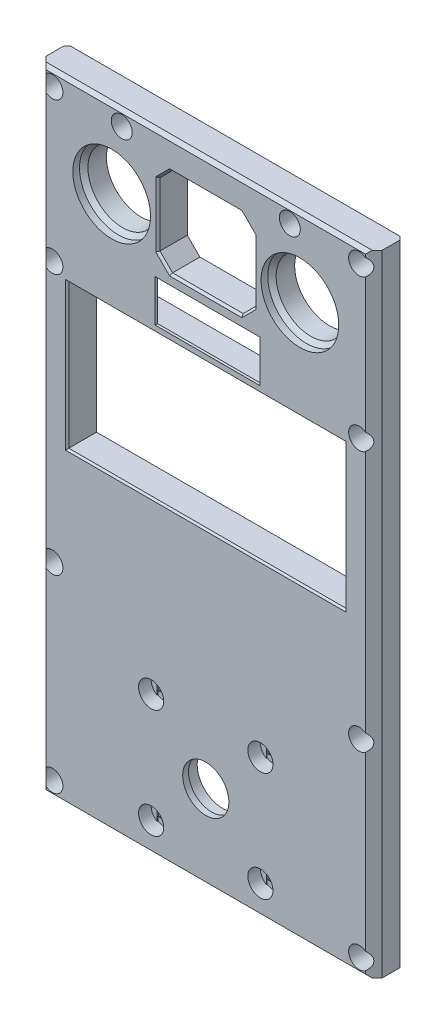
SolidWorks part; units mm, degrees
ref_plane "Front Plane" through (0, 0, 0) normal (0, 0, 1) x (1, 0, 0)
ref_plane "Top Plane" through (0, 0, 0) normal (0, 1, 0) x (1, 0, 0)
ref_plane "Right Plane" through (0, 0, 0) normal (1, 0, 0) x (0, 0, -1)
sketch "Sketch1" plane through (0, 0, 0) normal (0, 0, 1) x (1, 0, 0)
  line L1 (-40, -75) -> (40, -75)
  line L2 (-40, -75) -> (-40, 75)
  line L3 (-40, 75) -> (40, 75)
  line L4 (40, -75) -> (40, 75)
  line L5 (-40, -75) -> (40, 75) construction
  line L6 (-40, 75) -> (40, -75) construction
  line L7 (-33, -68) -> (33, -68)
  line L8 (-33, -68) -> (-33, 68)
  line L9 (-33, 68) -> (33, 68)
  line L10 (33, -68) -> (33, 68)
  line L11 (-33, -68) -> (33, 68) construction
  line L12 (-33, 68) -> (33, -68) construction
  point P0 (0, 0)
  point P6 (0, 0)
  dimension "D1" = 150
  dimension "D2" = 80
  dimension "D3" = 7
  dimension "D4" = 7
extrude "Boss-Extrude1" add sketch "Sketch1" along normal blind 7
sketch "Sketch2" plane through (0, 0, 7) normal (0, 0, 1) x (1, 0, 0)
  line L0 (33, -68) -> (33, 68) construction
  line L1 (-33, -68) -> (33, -68)
  line L2 (-33, -68) -> (-33, -32)
  line L3 (-33, -32) -> (33, -32)
  line L4 (33, -68) -> (33, -32)
  dimension "D1" = 36
extrude "Boss-Extrude2" add sketch "Sketch2" against normal up to surface (7 mm away) up to face at (0, 0, 0)
sketch "Sketch3" plane through (0, 0, 0) normal (0, 0, -1) x (-1, 0, 0)
  line L0 (0, -75) -> (0, -55) construction
  line L1 (40, -75) -> (-40, -75) construction
  circle A0 centre (0, -55) radius 5.5
  dimension "D1" = 11
  dimension "D2" = 20
extrude "Cut-Extrude1" cut sketch "Sketch3" against normal through all
sketch "Sketch4" plane through (0, 0, 0) normal (0, 0, -1) x (-1, 0, 0)
  circle A0 centre (0, -55) radius 6.05
  dimension "D1" = 12.1
extrude "Cut-Extrude2" cut sketch "Sketch4" against normal offset from surface (5.6 mm away) 1.4 up to face at (-5.5, -55, 7)
sketch "Sketch5" plane through (0, 0, 0) normal (0, 0, -1) x (-1, 0, 0)
  circle A0 centre (0, -55) radius 11.1
  dimension "D1" = 22.2
extrude "Cut-Extrude3" cut sketch "Sketch5" against normal offset from surface (3 mm away) 2.6 up to face at (-6.05, -55, 5.6)
sketch "Sketch6" plane through (0, 0, 0) normal (0, 0, -1) x (-1, 0, 0)
  line L1 (-13, -68) -> (13, -68) construction
  line L2 (-13, -68) -> (-13, -42) construction
  line L3 (-13, -42) -> (13, -42) construction
  line L4 (13, -68) -> (13, -42) construction
  line L5 (-13, -68) -> (13, -42) construction
  line L6 (-13, -42) -> (13, -68) construction
  circle A0 centre (-13, -42) radius 1.6
  circle A1 centre (13, -42) radius 1.6
  circle A2 centre (13, -68) radius 1.6
  circle A3 centre (-13, -68) radius 1.6
  point P0 (0, -55)
  dimension "D2" = 3.2
  dimension "D1" = 26
extrude "Cut-Extrude4" cut sketch "Sketch6" against normal through all
sketch "Sketch7" plane through (0, 0, 0) normal (0, 0, -1) x (-1, 0, 0)
  line L1 (-25, -74) -> (25, -74)
  line L2 (-25, -74) -> (-25, -36)
  line L3 (-25, -36) -> (25, -36)
  line L4 (25, -74) -> (25, -36)
  line L5 (-25, -74) -> (25, -36) construction
  line L6 (-25, -36) -> (25, -74) construction
  point P0 (0, -55)
  dimension "D1" = 50
  dimension "D2" = 38
extrude "Cut-Extrude5" cut sketch "Sketch7" against normal blind 1
sketch "Sketch8" plane through (0, 0, 7) normal (0, 0, 1) x (1, 0, 0)
  circle A0 centre (-13, -42) radius 3
  circle A1 centre (13, -42) radius 3
  circle A2 centre (13, -68) radius 3
  circle A3 centre (-13, -68) radius 3
  dimension "D1" = 6
extrude "Cut-Extrude6" cut sketch "Sketch8" against normal blind 3
sketch "Sketch9" plane through (0, 0, 7) normal (0, 0, 1) x (1, 0, 0)
  line L0 (-40, 75) -> (-40, -75) construction
  line L1 (-36.5, -71.5) -> (36.5, -71.5) construction
  line L2 (-36.5, -71.5) -> (-36.5, 71.5) construction
  line L3 (-36.5, 71.5) -> (36.5, 71.5) construction
  line L4 (36.5, -71.5) -> (36.5, 71.5) construction
  line L5 (-36.5, -71.5) -> (36.5, 71.5) construction
  line L6 (-36.5, 71.5) -> (36.5, -71.5) construction
  line L7 (40, 75) -> (-40, 75) construction
  circle A0 centre (-36.5, 71.5) radius 1.35
  circle A1 centre (36.5, 71.5) radius 1.35
  circle A2 centre (36.5, -71.5) radius 1.35
  circle A3 centre (-36.5, -71.5) radius 1.35
  circle A6 centre (-36.5, 35.5) radius 1.35
  circle A7 centre (-36.5, -26.5) radius 1.35
  circle A8 centre (36.5, -26.5) radius 1.35
  circle A9 centre (36.5, 35.5) radius 1.35
  point P0 (0, 0)
  dimension "D3" = 2.7
  dimension "D4" = 45
  dimension "D5" = 36
  dimension "D1" = 3.5
  dimension "D2" = 3.5
extrude "Cut-Extrude7" cut sketch "Sketch9" against normal through all
sketch "Sketch10" plane through (0, 0, 7) normal (0, 0, 1) x (1, 0, 0)
  circle A0 centre (-36.5, 71.5) radius 2.5
  circle A1 centre (36.5, 71.5) radius 2.5
  circle A2 centre (-36.5, 35.5) radius 2.5
  circle A3 centre (-36.5, -26.5) radius 2.5
  circle A4 centre (-36.5, -71.5) radius 2.5
  circle A5 centre (36.5, -71.5) radius 2.5
  circle A6 centre (36.5, 35.5) radius 2.5
  circle A7 centre (36.5, -26.5) radius 2.5
  dimension "D1" = 5
extrude "Cut-Extrude8" cut sketch "Sketch10" against normal blind 5
chamfer "Chamfer1" distance 2 angle 45 2 edges at (-40, 0, 7) (40, 0, 7)
sketch "Sketch11" plane through (0, 0, 7) normal (0, 0, 1) x (1, 0, 0)
  line L0 (33, -32) -> (33, 68) construction
  line L1 (-33, -32) -> (33, -32)
  line L2 (-33, -32) -> (-33, -1.5)
  line L3 (-33, -1.5) -> (33, -1.5)
  line L4 (33, -32) -> (33, -1.5)
  line L5 (-38, -75) -> (38, -75) construction
  dimension "D1" = 73.5
extrude "Boss-Extrude3" add sketch "Sketch11" against normal up to surface (7 mm away) up to face at (37.85, 71.5, 0)
sketch "Sketch12" plane through (0, 0, 2) normal (0, 0, 1) x (1, 0, 0)
  line L2 (-37.85, -73.6042) -> (-37.85, -69.3958)
  line L4 (-35.15, -73.6042) -> (-35.15, -69.3958)
  line L5 (-37.85, -73.6042) -> (-35.15, -69.3958) construction
  line L6 (-37.85, -69.3958) -> (-35.15, -73.6042) construction
  line L8 (-37.85, -28.6042) -> (-37.85, -24.3958)
  line L10 (-35.15, -28.6042) -> (-35.15, -24.3958)
  line L11 (-37.85, -28.6042) -> (-35.15, -24.3958) construction
  line L12 (-37.85, -24.3958) -> (-35.15, -28.6042) construction
  line L14 (-37.85, 33.3958) -> (-37.85, 37.6042)
  line L16 (-35.15, 33.3958) -> (-35.15, 37.6042)
  line L17 (-37.85, 33.3958) -> (-35.15, 37.6042) construction
  line L18 (-37.85, 37.6042) -> (-35.15, 33.3958) construction
  line L20 (-37.85, 69.3958) -> (-37.85, 73.6042)
  line L22 (-35.15, 69.3958) -> (-35.15, 73.6042)
  line L23 (-37.85, 69.3958) -> (-35.15, 73.6042) construction
  line L24 (-37.85, 73.6042) -> (-35.15, 69.3958) construction
  arc A0 (-38, -73.5) -> (-38, -69.5) centre (-36.5, -71.5) ccw construction
  circle A1 centre (-36.5, -26.5) radius 2.5 construction
  circle A2 centre (-36.5, 35.5) radius 2.5 construction
  arc A3 (-38, 69.5) -> (-38, 73.5) centre (-36.5, 71.5) ccw construction
  circle A4 centre (-36.5, 71.5) radius 1.35 construction
  circle A5 centre (-36.5, 71.5) radius 2.5 construction
  arc A6 (-35.15, 73.6042) -> (-37.85, 73.6042) centre (-36.5, 71.5) ccw
  arc A7 (-37.85, 69.3958) -> (-35.15, 69.3958) centre (-36.5, 71.5) ccw
  circle A8 centre (-36.5, 35.5) radius 1.35 construction
  arc A9 (-37.85, 33.3958) -> (-35.15, 33.3958) centre (-36.5, 35.5) ccw
  arc A10 (-35.15, 37.6042) -> (-37.85, 37.6042) centre (-36.5, 35.5) ccw
  circle A11 centre (-36.5, -26.5) radius 1.35 construction
  arc A12 (-37.85, -28.6042) -> (-35.15, -28.6042) centre (-36.5, -26.5) ccw
  arc A13 (-35.15, -24.3958) -> (-37.85, -24.3958) centre (-36.5, -26.5) ccw
  circle A14 centre (-36.5, -71.5) radius 1.35 construction
  arc A16 (-37.85, -73.6042) -> (-35.15, -73.6042) centre (-36.5, -71.5) ccw
  arc A18 (-35.15, -69.3958) -> (-37.85, -69.3958) centre (-36.5, -71.5) ccw
  point P0 (-36.5, -71.5)
  point P9 (-36.5, -26.5)
  point P17 (-36.5, 35.5)
  point P25 (-36.5, 71.5)
extrude "Cut-Extrude9" cut sketch "Sketch12" against normal blind 0.2
sketch "Sketch13" plane through (0, 0, 1.8) normal (0, 0, 1) x (1, 0, 0)
  line L0 (-35.15, -71.5) -> (-35.15, -69.3958) construction
  line L1 (-37.85, -72.85) -> (-35.15, -72.85)
  line L2 (-37.85, -72.85) -> (-37.85, -70.15)
  line L3 (-37.85, -70.15) -> (-35.15, -70.15)
  line L4 (-35.15, -72.85) -> (-35.15, -70.15)
  line L5 (-37.85, -72.85) -> (-35.15, -70.15) construction
  line L6 (-37.85, -70.15) -> (-35.15, -72.85) construction
  line L7 (-35.15, -26.5) -> (-35.15, -24.3958) construction
  line L8 (-37.85, -27.85) -> (-35.15, -27.85)
  line L9 (-37.85, -27.85) -> (-37.85, -25.15)
  line L10 (-37.85, -25.15) -> (-35.15, -25.15)
  line L11 (-35.15, -27.85) -> (-35.15, -25.15)
  line L12 (-37.85, -27.85) -> (-35.15, -25.15) construction
  line L13 (-37.85, -25.15) -> (-35.15, -27.85) construction
  line L14 (-35.15, 33.3958) -> (-35.15, 37.6042) construction
  line L15 (-37.85, 34.15) -> (-35.15, 34.15)
  line L16 (-37.85, 34.15) -> (-37.85, 36.85)
  line L17 (-37.85, 36.85) -> (-35.15, 36.85)
  line L18 (-35.15, 34.15) -> (-35.15, 36.85)
  line L19 (-37.85, 34.15) -> (-35.15, 36.85) construction
  line L20 (-37.85, 36.85) -> (-35.15, 34.15) construction
  line L21 (-35.15, 69.3958) -> (-35.15, 73.6042) construction
  line L22 (-37.85, 70.15) -> (-35.15, 70.15)
  line L23 (-37.85, 70.15) -> (-37.85, 72.85)
  line L24 (-37.85, 72.85) -> (-35.15, 72.85)
  line L25 (-35.15, 70.15) -> (-35.15, 72.85)
  line L26 (-37.85, 70.15) -> (-35.15, 72.85) construction
  line L27 (-37.85, 72.85) -> (-35.15, 70.15) construction
  arc A0 (-35.15, -71.5) -> (-37.85, -71.5) centre (-36.5, -71.5) ccw construction
  arc A1 (-35.15, -26.5) -> (-37.85, -26.5) centre (-36.5, -26.5) ccw construction
  arc A2 (-35.15, 35.5) -> (-37.85, 35.5) centre (-36.5, 35.5) ccw construction
  arc A3 (-35.15, 71.5) -> (-37.85, 71.5) centre (-36.5, 71.5) ccw construction
  point P0 (-36.5, -71.5)
  point P11 (-36.5, -26.5)
  point P22 (-36.5, 35.5)
  point P33 (-36.5, 71.5)
extrude "Cut-Extrude10" cut sketch "Sketch13" against normal blind 0.2
sketch "Sketch14" plane through (0, 0, 4) normal (0, 0, 1) x (1, 0, 0)
  line L2 (-14.6, -44.5377) -> (-14.6, -39.4623)
  line L4 (-11.4, -44.5377) -> (-11.4, -39.4623)
  line L5 (-14.6, -44.5377) -> (-11.4, -39.4623) construction
  line L6 (-14.6, -39.4623) -> (-11.4, -44.5377) construction
  line L8 (-14.6, -70.5377) -> (-14.6, -65.4623)
  line L10 (-11.4, -70.5377) -> (-11.4, -65.4623)
  line L11 (-14.6, -70.5377) -> (-11.4, -65.4623) construction
  line L12 (-14.6, -65.4623) -> (-11.4, -70.5377) construction
  circle A0 centre (-13, -42) radius 3 construction
  circle A1 centre (-13, -68) radius 3 construction
  circle A2 centre (-13, -42) radius 3 construction
  arc A3 (-14.6, -44.5377) -> (-11.4, -44.5377) centre (-13, -42) ccw
  arc A4 (-14.6, -70.5377) -> (-11.4, -70.5377) centre (-13, -68) ccw
  circle A5 centre (-13, -42) radius 1.6 construction
  circle A6 centre (-13, -68) radius 1.6 construction
  arc A7 (-11.4, -39.4623) -> (-14.6, -39.4623) centre (-13, -42) ccw
  arc A8 (-11.4, -65.4623) -> (-14.6, -65.4623) centre (-13, -68) ccw
  point P0 (-13, -42)
  point P8 (-13, -68)
extrude "Cut-Extrude11" cut sketch "Sketch14" against normal blind 0.2
sketch "Sketch15" plane through (0, 0, 3.8) normal (0, 0, 1) x (1, 0, 0)
  line L0 (-11.4, -42) -> (-11.4, -39.4623) construction
  line L1 (-14.6, -43.6) -> (-11.4, -43.6)
  line L2 (-14.6, -43.6) -> (-14.6, -40.4)
  line L3 (-14.6, -40.4) -> (-11.4, -40.4)
  line L4 (-11.4, -43.6) -> (-11.4, -40.4)
  line L5 (-14.6, -43.6) -> (-11.4, -40.4) construction
  line L6 (-14.6, -40.4) -> (-11.4, -43.6) construction
  line L7 (-11.4, -68) -> (-11.4, -65.4623) construction
  line L8 (-14.6, -69.6) -> (-11.4, -69.6)
  line L9 (-14.6, -69.6) -> (-14.6, -66.4)
  line L10 (-14.6, -66.4) -> (-11.4, -66.4)
  line L11 (-11.4, -69.6) -> (-11.4, -66.4)
  line L12 (-14.6, -69.6) -> (-11.4, -66.4) construction
  line L13 (-14.6, -66.4) -> (-11.4, -69.6) construction
  arc A0 (-11.4, -68) -> (-14.6, -68) centre (-13, -68) ccw construction
  arc A1 (-14.6, -42) -> (-11.4, -42) centre (-13, -42) ccw construction
  point P0 (-13, -42)
  point P8 (-13, -68)
extrude "Cut-Extrude12" cut sketch "Sketch15" against normal blind 0.2
mirror "Mirror1" about plane through (0, 0, 0) normal (1, 0, 0) of "Cut-Extrude10", "Cut-Extrude11", "Cut-Extrude12", "Cut-Extrude9"
chamfer "Chamfer2" distance 0.4 angle 45 4 edges at (33, 33.25, 7) (0, 68, 7) (0, -1.5, 7) (-33, 33.25, 7)
chamfer "Chamfer3" distance 0.8 angle 45 4 edges at (-40, 0, 0) (40, 0, 0) (0, -75, 7) (0, 75, 7)
sketch "Sketch16" plane through (0, 0, 0) normal (1, 0, 0) x (0, 0, -1)
  line L0 (0, -4) -> (0, -15.4)
  line L1 (0, 75) -> (0, -75) construction
  line L2 (0, -15.4) -> (3.2, -12.2)
  line L3 (3.2, -12.2) -> (3.2, -7.2)
  line L4 (3.2, -7.2) -> (0, -4)
  line L5 (0, -15.4) -> (0, -19.4) construction
  line L6 (0.6, -7.7) -> (2.6, -7.7)
  line L7 (0.6, -7.7) -> (0.6, -11.7)
  line L8 (0.6, -11.7) -> (2.6, -11.7)
  line L9 (2.6, -7.7) -> (2.6, -11.7)
  line L10 (-1.046, -17.4) -> (12.8392, -17.4) construction
  line L11 (2.6, -27.1) -> (2.6, -23.1)
  line L12 (0.6, -23.1) -> (2.6, -23.1)
  line L13 (0.6, -27.1) -> (0.6, -23.1)
  line L14 (0.6, -27.1) -> (2.6, -27.1)
  line L15 (3.2, -27.6) -> (0, -30.8)
  line L16 (3.2, -22.6) -> (3.2, -27.6)
  line L17 (0, -19.4) -> (3.2, -22.6)
  line L18 (0, -30.8) -> (0, -19.4)
  point P10 (2.6, -9.7)
  point P11 (3.2, -9.7)
  point P24 (0, -17.4)
  dimension "D1" = 5
  dimension "D2" = 2
  dimension "D3" = 0.6
  dimension "D4" = 0.6
  dimension "D5" = 45
  dimension "D6" = 4
  dimension "D7" = 4
  dimension "D8" = 4
extrude "Boss-Extrude4" add sketch "Sketch16" along normal mid plane 2
pattern_linear "LPattern1" count 2 spacing 20 along (1, 0, 0) count 2 spacing 20 along (-1, 0, 0) of "Boss-Extrude4"
sketch "Sketch17" plane through (0, 0, 0) normal (0, 0, -1) x (-1, 0, 0)
  line L0 (-20, 71.5) -> (20, 71.5) construction
  line L1 (-39.2, 75) -> (39.2, 75) construction
  circle A0 centre (-36.5, 71.5) radius 1.35 construction
  circle A1 centre (-36.5, 71.5) radius 1.35 construction
  circle A2 centre (-20, 71.5) radius 1.35
  circle A3 centre (20, 71.5) radius 1.35
  point P3 (0, 71.5)
  point P6 (0, 75)
  dimension "D1" = 40
extrude "Cut-Extrude13" cut sketch "Sketch17" against normal through all
sketch "Sketch18" plane through (0, 0, 7) normal (0, 0, 1) x (1, 0, 0)
  circle A0 centre (-20, 71.5) radius 2.5
  circle A1 centre (20, 71.5) radius 2.5
  arc A2 (-38, 69.5) -> (-38, 73.5) centre (-36.5, 71.5) ccw construction
extrude "Cut-Extrude14" cut sketch "Sketch18" against normal up to surface (5 mm away) up to face at (34.575, 71.5, 2)
sketch "Sketch19" plane through (0, 0, 2) normal (0, 0, 1) x (1, 0, 0)
  line L2 (-21.35, 69.3958) -> (-21.35, 73.6042)
  line L4 (-18.65, 69.3958) -> (-18.65, 73.6042)
  line L5 (-21.35, 69.3958) -> (-18.65, 73.6042) construction
  line L6 (-21.35, 73.6042) -> (-18.65, 69.3958) construction
  line L8 (18.65, 69.3958) -> (18.65, 73.6042)
  line L10 (21.35, 69.3958) -> (21.35, 73.6042)
  line L11 (18.65, 69.3958) -> (21.35, 73.6042) construction
  line L12 (18.65, 73.6042) -> (21.35, 69.3958) construction
  circle A0 centre (-20, 71.5) radius 2.5 construction
  circle A1 centre (20, 71.5) radius 2.5 construction
  circle A2 centre (20, 71.5) radius 1.35 construction
  circle A3 centre (-20, 71.5) radius 1.35 construction
  circle A4 centre (-20, 71.5) radius 2.5 construction
  arc A5 (18.65, 69.3958) -> (21.35, 69.3958) centre (20, 71.5) ccw
  arc A6 (-18.65, 73.6042) -> (-21.35, 73.6042) centre (-20, 71.5) ccw
  arc A7 (21.35, 73.6042) -> (18.65, 73.6042) centre (20, 71.5) ccw
  arc A8 (-21.35, 69.3958) -> (-18.65, 69.3958) centre (-20, 71.5) ccw
  point P0 (-20, 71.5)
  point P8 (20, 71.5)
extrude "Cut-Extrude15" cut sketch "Sketch19" against normal blind 0.2
sketch "Sketch20" plane through (0, 0, 1.8) normal (0, 0, 1) x (1, 0, 0)
  line L0 (-18.65, 69.3958) -> (-18.65, 73.6042) construction
  line L1 (-21.35, 70.15) -> (-18.65, 70.15)
  line L2 (-21.35, 70.15) -> (-21.35, 72.85)
  line L3 (-21.35, 72.85) -> (-18.65, 72.85)
  line L4 (-18.65, 70.15) -> (-18.65, 72.85)
  line L5 (-21.35, 70.15) -> (-18.65, 72.85) construction
  line L6 (-21.35, 72.85) -> (-18.65, 70.15) construction
  line L7 (21.35, 71.5) -> (21.35, 73.6042) construction
  line L8 (18.65, 70.15) -> (21.35, 70.15)
  line L9 (18.65, 70.15) -> (18.65, 72.85)
  line L10 (18.65, 72.85) -> (21.35, 72.85)
  line L11 (21.35, 70.15) -> (21.35, 72.85)
  line L12 (18.65, 70.15) -> (21.35, 72.85) construction
  line L13 (18.65, 72.85) -> (21.35, 70.15) construction
  arc A0 (18.65, 71.5) -> (21.35, 71.5) centre (20, 71.5) ccw construction
  point P0 (-20, 71.5)
  point P8 (20, 71.5)
extrude "Cut-Extrude16" cut sketch "Sketch20" against normal blind 0.2
sketch "Skizze4" plane through (0, 0, 0) normal (0, 0, -1) x (-1, 0, 0)
  line L1 (21, -4) -> (-21, -4)
  line L2 (21, -4) -> (21, -30.8)
  line L3 (21, -30.8) -> (-21, -30.8)
  line L4 (-21, -4) -> (-21, -30.8)
extrude "Schnitt-Linear austragen1" cut sketch "Skizze4" along normal up to surface (3.2 mm away) up to face at (-20, -9.7, -3.2)
sketch "Skizze6" plane through (0, 0, 7) normal (0, 0, 1) x (1, 0, 0)
  line L0 (11.4, 68.4) -> (33.4, 46.4) construction
  line L1 (33.4, 68.4) -> (11.4, 68.4)
  line L2 (33.4, 68.4) -> (33.4, 46.4)
  line L3 (33.4, 46.4) -> (11.4, 46.4)
  line L4 (11.4, 68.4) -> (11.4, 46.4)
  line L5 (22.4, 68.4) -> (22.4, 46.4) construction
  circle A0 centre (22.4, 56.4) radius 8.25
  point P10 (22.4, 57.4)
  dimension "D1" = 16.5
  dimension "D2" = 22
  dimension "D3" = 22
  dimension "D4" = 1
extrude "Aufsatz-Linear austragen1" add sketch "Skizze6" against normal up to surface (7 mm away) up to face at (18.65, 71.5, 0)
sketch "Skizze7" plane through (0, 0, 7) normal (0, 0, 1) x (1, 0, 0)
  circle A0 centre (22.4, 56.4) radius 9.25
  dimension "D1" = 18.5
extrude "Schnitt-Linear austragen2" cut sketch "Skizze7" against normal blind 1.6
chamfer "Fase6" distance 0.5 angle 45 2 edges at (11.4, 57.4, 7) (22.4, 46.4, 7)
chamfer "Fase7" distance 4 angle 45 1 edges at (11.4, 46.4, 3.25)
chamfer "Fase8" distance 1 angle 45 1 edges at (30.65, 56.4, 5.4)
mirror "Mirror2" about plane through (0, 0, 0) normal (1, 0, 0) of "Fase6", "Schnitt-Linear austragen2", "Fase8", "Aufsatz-Linear austragen1", "Fase7"
sketch "Sketch21" plane through (0, 0, 7) normal (0, 0, 1) x (1, 0, 0)
  line L0 (33.4, 46.9) -> (33.4, -1.9) construction
  line L1 (-33.4, 46.9) -> (-14.9, 46.9)
  line L2 (-33.4, 46.9) -> (-33.4, 32.9)
  line L3 (-33.4, 32.9) -> (33.4, 32.9)
  line L4 (33.4, 46.9) -> (33.4, 32.9)
  line L5 (-14.9, 46.9) -> (-11.4, 50.4)
  line L6 (-11.4, 50.4) -> (-11.4, 46.9)
  line L7 (11.4, 50.4) -> (14.9, 46.9)
  line L8 (11.4, 50.4) -> (11.4, 46.9)
  line L9 (-11.4, 46.9) -> (11.4, 46.9)
  line L10 (14.9, 46.9) -> (33.4, 46.9)
  dimension "D1" = 14
extrude "Boss-Extrude5" add sketch "Sketch21" against normal up to surface (7 mm away) up to face at (0, 41.94, 0)
chamfer "Chamfer4" distance 0.5 angle 45 3 edges at (11.4, 48.65, 7) (-11.4, 48.65, 7) (0, 46.9, 7)
sketch "Sketch22" plane through (0, 0, 0) normal (0, 0, -1) x (-1, 0, 0)
  line L0 (0, 46.9) -> (0, 32.9) construction
  line L1 (-11.4, 46.9) -> (11.4, 46.9) construction
  line L2 (33, 32.9) -> (-33, 32.9) construction
  line L4 (-18.95, 33.75) -> (18.95, 33.75)
  line L5 (-18.95, 33.75) -> (-18.95, 46.05)
  line L6 (-18.95, 46.05) -> (18.95, 46.05)
  line L7 (18.95, 33.75) -> (18.95, 46.05)
  line L8 (-18.95, 33.75) -> (18.95, 46.05) construction
  line L9 (-18.95, 46.05) -> (18.95, 33.75) construction
  point P6 (0, 39.9)
  dimension "D1" = 37.9
  dimension "D2" = 12.3
extrude "Cut-Extrude17" cut sketch "Sketch22" against normal offset from surface (6.4 mm away) 0.6 up to face at (0, 15.5, 7)
sketch "Sketch23" plane through (0, 0, 6.4) normal (0, 0, -1) x (-1, 0, 0)
  line L0 (-18.95, 46.05) -> (-18.95, 33.75) construction
  line L1 (-12.95, 34.55) -> (12.05, 34.55)
  line L2 (-12.95, 34.55) -> (-12.95, 44.55)
  line L3 (-12.95, 44.55) -> (12.05, 44.55)
  line L4 (12.05, 34.55) -> (12.05, 44.55)
  line L5 (-12.95, 34.55) -> (12.05, 44.55) construction
  line L6 (-12.95, 44.55) -> (12.05, 34.55) construction
  line L7 (-18.95, 46.05) -> (18.95, 46.05) construction
  point P0 (-0.45, 39.55)
  dimension "D1" = 25
  dimension "D2" = 10
  dimension "D3" = 6
  dimension "D4" = 1.5
extrude "Cut-Extrude18" cut sketch "Sketch23" against normal through all
chamfer "Chamfer5" distance 0.4 angle 45 1 edges at (0, 32.9, 7)
sketch "Sketch24" plane through (0, 0, 7) normal (0, 0, 1) x (1, 0, 0)
  line L1 (-11.9, 68.4) -> (11.9, 68.4)
  line L2 (-11.9, 68.4) -> (-11.9, 46.4)
  line L3 (-11.9, 46.4) -> (11.9, 46.4)
  line L4 (11.9, 68.4) -> (11.9, 46.4)
  line L5 (-11.4, 68) -> (11.4, 68)
  line L6 (-11.4, 68) -> (-11.4, 46.9)
  line L7 (-11.4, 46.9) -> (11.4, 46.9)
  line L8 (11.4, 68) -> (11.4, 46.9)
extrude "Boss-Extrude6" add sketch "Sketch24" against normal up to vertex (0.5 mm away) up to point (11.4, 46.9, 6.5)
chamfer "Chamfer7" distance 3 angle 45 4 edges at (11.4, 46.9, 3.5) (11.4, 68, 3.5) (-11.4, 68, 3.5) (-11.4, 46.9, 3.5)
chamfer "Chamfer8" distance 0.5 angle 45 8 edges at (-9.9, 48.4, 7) (0, 46.9, 7) (9.9, 48.4, 7) (11.4, 57.45, 7) (9.9, 66.5, 7) (0, 68, 7) (-9.9, 66.5, 7) (-11.4, 57.45, 7)
